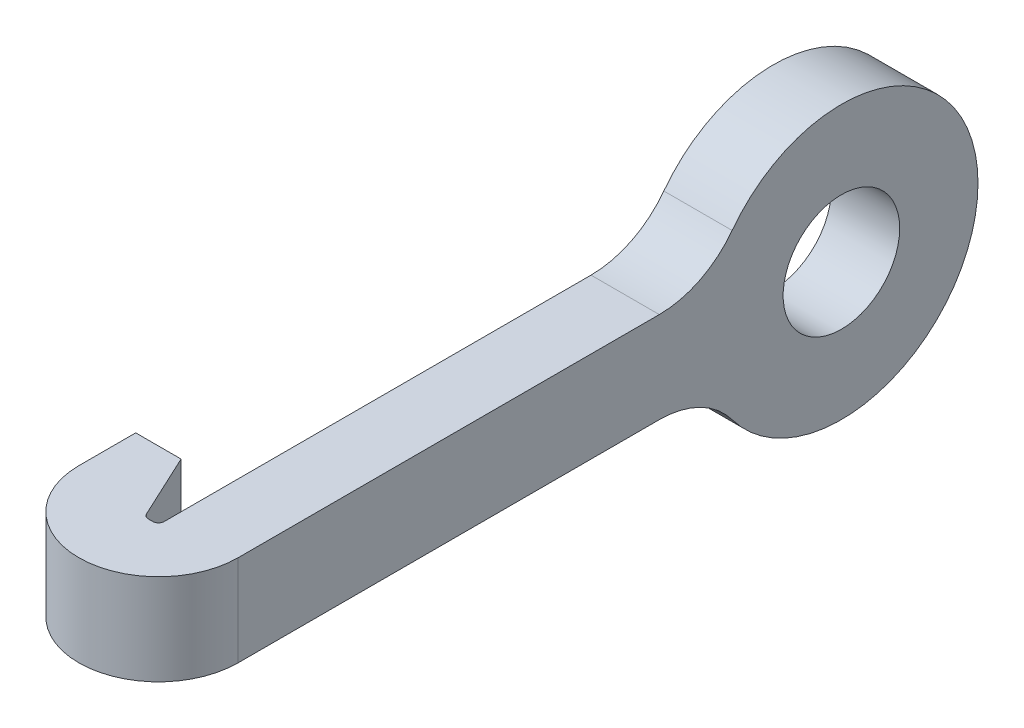
SolidWorks part; units mm, degrees
material "Polycarbonate"
ref_plane "Front Plane" through (0, 0, 0) normal (0, 0, 1) x (1, 0, 0)
ref_plane "Top Plane" through (0, 0, 0) normal (0, 1, 0) x (1, 0, 0)
ref_plane "Right Plane" through (0, 0, 0) normal (1, 0, 0) x (0, 0, -1)
sketch "Sketch1" plane through (0, 0, 0) normal (0, 1, 0) x (1, 0, 0)
  line L0 (0, 0) -> (-7.9375, 0)
  line L13 (0, 0) -> (3.175, 0)
  line L14 (-1.5875, 4.7625) -> (-1.5875, 38.1)
  line L15 (-1.5875, 38.1) -> (3.175, 38.1)
  line L16 (3.175, 0) -> (3.175, 38.1)
  line L17 (-7.9375, 0) -> (-7.9375, 9.525)
  line L18 (-7.9375, 9.525) -> (-4.7735, 9.525)
  line L19 (-4.7735, 9.525) -> (-2.5527, 4.7625)
  line L20 (-2.5527, 4.7625) -> (-1.5875, 4.7625)
  dimension "D1" = 4.7625
  dimension "D2" = 6.35
  dimension "D3" = 9.525
  dimension "D4" = 25
  dimension "D5" = 4.7625
  dimension "D6" = 0.9652
  dimension "D8" = 38.1
extrude "Boss-Extrude1" add sketch "Sketch1" along normal blind 6.35
fillet "Fillet1" radius 0.3969 2 edges at (-2.5527, 3.175, -4.7625) (-1.5875, 3.175, -4.7625)
fillet "Fillet3" 2 edges at (-7.9375, 3.175, 0) (3.175, 3.175, 0) type full round first side face at (-7.9375, 3.175, -4.7625) second side face at (3.175, 3.175, -19.05) middle face at (-2.3812, 3.175, 0)
sketch "Sketch2" plane through (3.175, 0, 0) normal (1, 0, 0) x (0, 0, -1)
  line L0 (38.1, 6.35) -> (38.1, 0) construction
  line L1 (38.1, 6.35) -> (40.005, 8.89)
  line L2 (38.1, 0) -> (40.005, -2.54)
  line L3 (38.1, 6.35) -> (38.1, 0)
  arc A0 (40.005, -2.54) -> (40.005, 8.89) centre (47.625, 3.175) ccw
  circle A1 centre (47.625, 3.175) radius 4.064
  dimension "D1" = 19.05
  dimension "D2" = 8.128
extrude "Boss-Extrude2" add sketch "Sketch2" against normal up to surface (4.7625 mm away) up to face at (-1.5875, 3.175, -21.6297)
fillet "Fillet4" radius 6.35 2 edges at (0.7938, 0, -38.1) (0.7938, 6.35, -38.1)
